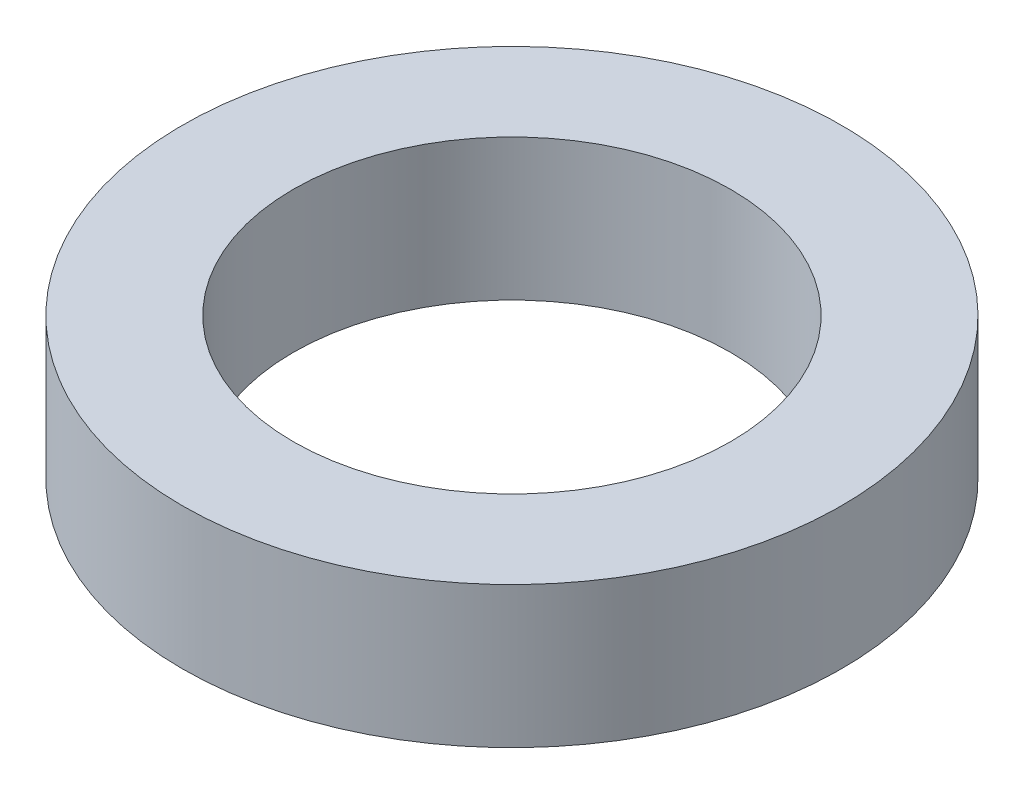
SolidWorks part; units mm, degrees
material "PET"
ref_plane "Front Plane" through (0, 0, 0) normal (0, 0, 1) x (1, 0, 0)
ref_plane "Top Plane" through (0, 0, 0) normal (0, 1, 0) x (1, 0, 0)
ref_plane "Right Plane" through (0, 0, 0) normal (1, 0, 0) x (0, 0, -1)
sketch "Sketch1" plane through (0, 0, 0) normal (0, 1, 0) x (1, 0, 0)
  circle A0 centre (0, 0) radius 7.2746
  circle A1 centre (0, 0) radius 4.826
  dimension "D1" = 9.652
  dimension "D2" = 14.5492
extrude "Boss-Extrude1" add sketch "Sketch1" along normal blind 3.1178
